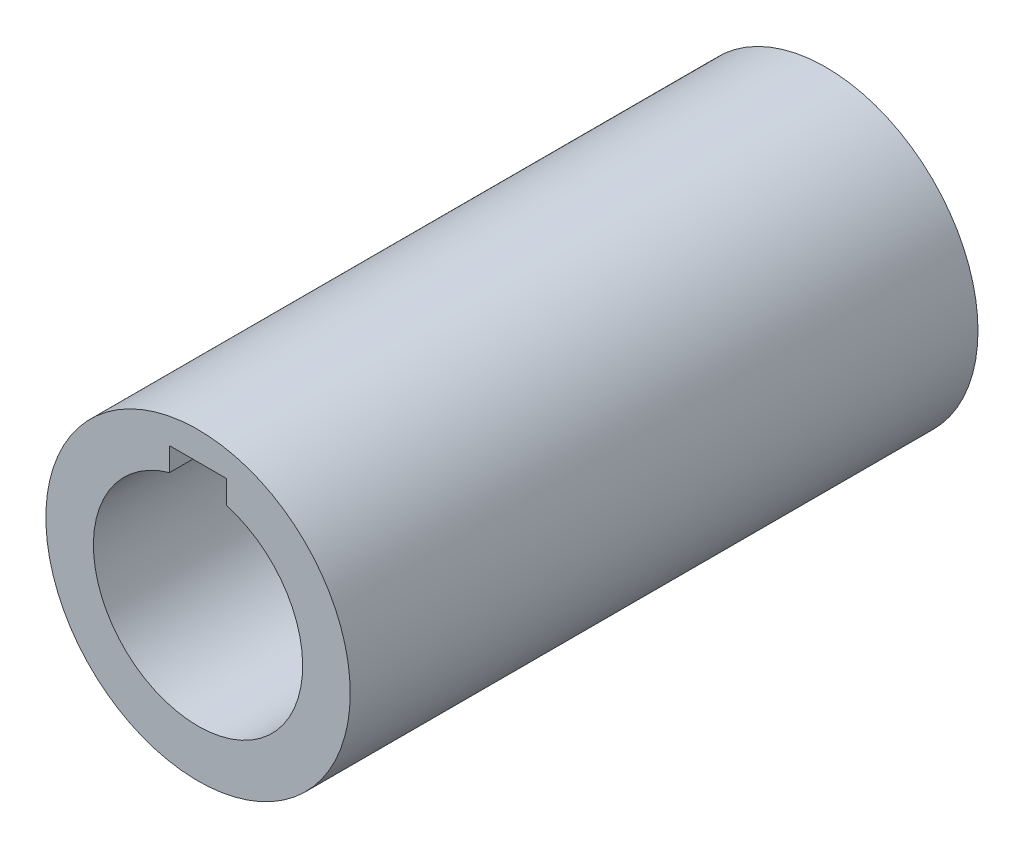
SolidWorks part; units mm, degrees
ref_plane "Front Plane" through (0, 0, 0) normal (0, 0, 1) x (1, 0, 0)
ref_plane "Top Plane" through (0, 0, 0) normal (0, 1, 0) x (1, 0, 0)
ref_plane "Right Plane" through (0, 0, 0) normal (1, 0, 0) x (0, 0, -1)
sketch "Sketch1" plane through (0, 0, 0) normal (0, 0, 1) x (1, 0, 0)
  circle A0 centre (0, 0) radius 11
  circle A1 centre (0, 0) radius 16
  dimension "D1" = 22
  dimension "D2" = 5
extrude "Boss-Extrude1" add sketch "Sketch1" along normal blind 33 and the other way blind 33
sketch "Sketch2" plane through (0, 0, 33) normal (0, 0, 1) x (1, 0, 0)
  line L0 (-3, 10.5402) -> (-3, 13.0402)
  line L2 (3, 13.0402) -> (3, 10.5402)
  line L3 (0, 0) -> (0, 13.0402) construction
  line L4 (-3, 13.0402) -> (0, 13.0402)
  line L5 (0, 13.0402) -> (3, 13.0402)
  line L6 (0, 0) -> (-3, 10.5402) construction
  line L7 (0, 0) -> (3, 10.5402) construction
  arc A0 (-3, 10.5402) -> (3, 10.5402) centre (0, 0) cw
  point P4 (0, 0)
  point P5 (-3, 12.5674)
  point P6 (-3, 12.5613)
  point P10 (-2.9947, 10.5216)
  dimension "D1" = 3
  dimension "D2" = 3
  dimension "D3" = 2.5
extrude "Cut-Extrude1" cut sketch "Sketch2" against normal blind 33
mirror "Mirror2" about plane through (0, 0, 0) normal (0, 0, -1) of "Cut-Extrude1"
